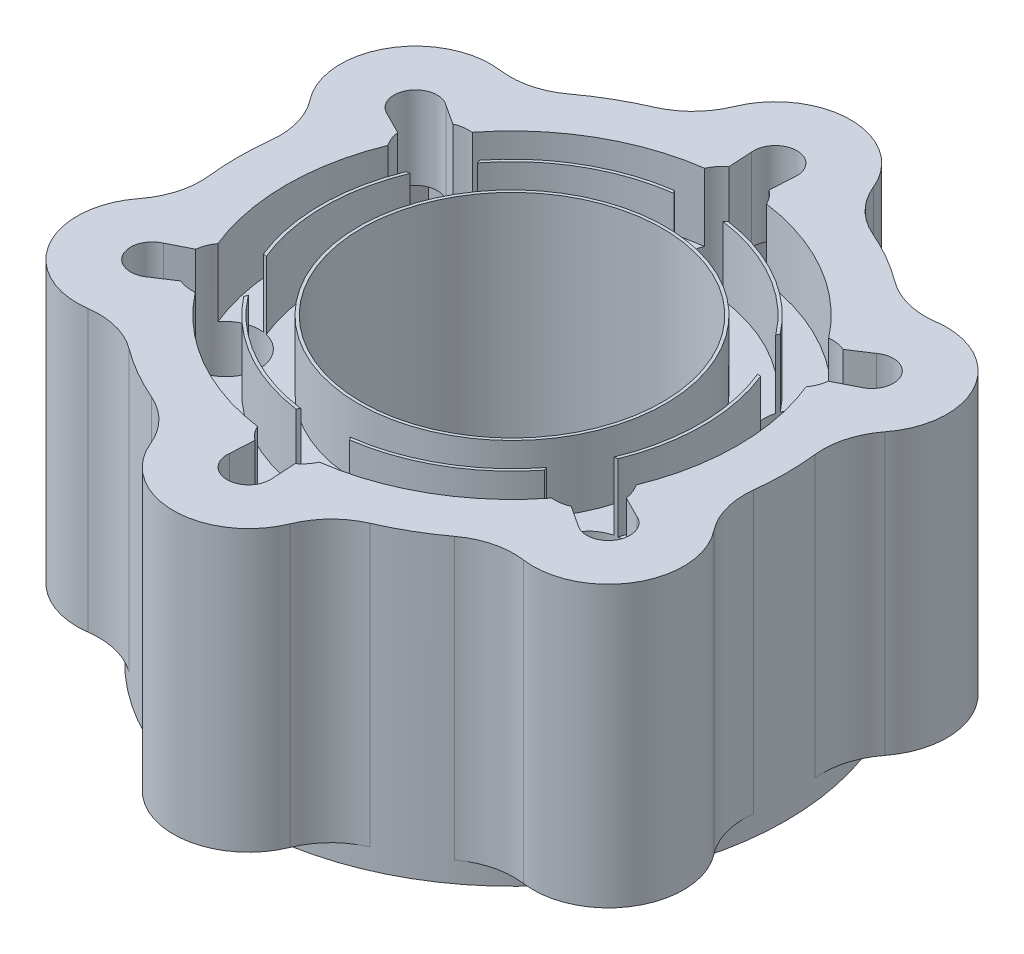
SolidWorks part; units mm, degrees
ref_plane "Front Plane" through (0, 0, 0) normal (0, 0, 1) x (1, 0, 0)
ref_plane "Top Plane" through (0, 0, 0) normal (0, 1, 0) x (1, 0, 0)
ref_plane "Right Plane" through (0, 0, 0) normal (1, 0, 0) x (0, 0, -1)
sketch "Sketch1" plane through (0, 0, 0) normal (0, 1, 0) x (1, 0, 0)
  circle A0 centre (0, 0) radius 27.875
  circle A1 centre (0, 0) radius 37
  circle A2 centre (0, 27.875) radius 2.375
  circle A3 centre (24.1405, 13.9375) radius 2.375
  circle A4 centre (24.1405, -13.9375) radius 2.375
  circle A5 centre (0, -27.875) radius 2.375
  circle A6 centre (-24.1405, -13.9375) radius 2.375
  circle A7 centre (-24.1405, 13.9375) radius 2.375
  circle A8 centre (0, 0) radius 20
  point P18 (0, 0)
  dimension "D1" = 55.75
  dimension "D2" = 74
  dimension "D3" = 4.75
  dimension "D5" = 40
  dimension "D4" = 6
extrude "Boss-Extrude1" add sketch "Sketch1" along normal blind 8 contours A1 A7 A0 A2 A3 A4 A5 A6 | A7 A0 A6 A5 A4 A3 A2 A8 region at (26.4399, 0, 5.8899) region at (-35.9535, 0, 0)
sketch "Sketch2" plane through (0, 8, 0) normal (0, 1, 0) x (1, 0, 0)
  circle A0 centre (0, 27.875) radius 4.5
  circle A1 centre (0, 0) radius 37
  circle A2 centre (0, 0) radius 37
  circle A3 centre (24.1405, 13.9375) radius 4.5
  circle A4 centre (24.1405, -13.9375) radius 4.5
  circle A5 centre (0, -27.875) radius 4.5
  circle A6 centre (-24.1405, -13.9375) radius 4.5
  circle A7 centre (-24.1405, 13.9375) radius 4.5
  circle A8 centre (0, 0) radius 20 construction
  circle A9 centre (0, 0) radius 20
  dimension "D2" = 9
  dimension "D1" = 0
extrude "Boss-Extrude2" add sketch "Sketch2" along normal offset from surface (32 mm away) 40 up to face at (-24.1405, 0, -11.5625)
sketch "Sketch3" plane through (0, 40, 0) normal (0, 1, 0) x (1, 0, 0)
  circle A0 centre (0, 0) radius 45
  circle A1 centre (0, 27.875) radius 4.5 construction
  circle A2 centre (24.1405, 13.9375) radius 4.5 construction
  circle A3 centre (24.1405, -13.9375) radius 4.5 construction
  circle A4 centre (0, -27.875) radius 4.5 construction
  circle A5 centre (0, 0) radius 20 construction
  circle A6 centre (-24.1405, 13.9375) radius 4.5 construction
  circle A7 centre (-24.1405, -13.9375) radius 4.5 construction
  circle A8 centre (0, 0) radius 20
  circle A9 centre (-24.1405, 13.9375) radius 4.5
  circle A10 centre (-24.1405, -13.9375) radius 4.5
  circle A11 centre (0, -27.875) radius 4.5
  circle A12 centre (24.1405, -13.9375) radius 4.5
  circle A13 centre (24.1405, 13.9375) radius 4.5
  circle A14 centre (0, 27.875) radius 4.5
  dimension "D1" = 90
extrude "Boss-Extrude3" add sketch "Sketch3" against normal offset from surface (37.25 mm away) 2.75 up to face at (-24.1405, 0, -11.5625)
sketch "Sketch4" plane through (0, 40, 0) normal (0, 1, 0) x (1, 0, 0)
  line L0 (-10, 35) -> (10, 35) construction
  circle A0 centre (0, 0) radius 35
  circle A1 centre (0, 35) radius 2.875
  circle A2 centre (30.3109, 17.5) radius 2.875
  circle A3 centre (30.3109, -17.5) radius 2.875
  circle A4 centre (0, -35) radius 2.875
  circle A5 centre (-30.3109, -17.5) radius 2.875
  circle A6 centre (-30.3109, 17.5) radius 2.875
  circle A7 centre (0, 35) radius 10
  circle A8 centre (30.3109, 17.5) radius 10
  circle A9 centre (30.3109, -17.5) radius 10
  circle A10 centre (0, -35) radius 10
  circle A11 centre (-30.3109, -17.5) radius 10
  circle A12 centre (-30.3109, 17.5) radius 10
  circle A13 centre (0, 0) radius 45 construction
  circle A14 centre (0, 0) radius 36.4005
  point P17 (0, 0)
  circle M17 centre (0, 0) radius 45
  dimension "D1" = 70
  dimension "D2" = 5.75
  dimension "D3" = 6
extrude "Cut-Extrude2" cut sketch "Sketch4" against normal up to next contours A14 A7 A12 M17 | A14 A8 A7 M17 | A14 A9 A8 M17 | A14 A10 A9 M17 | A14 A11 A10 M17 | A14 A12 A11 M17 | A1 | A2 | A3 | A4 | A5 | A6 region at (40.4878, 40, 0) region at (20.2439, 40, -35.0635) region at (20.2439, 40, 35.0635) region at (-20.2439, 40, -35.0635) region at (-20.2439, 40, 35.0635) region at (-40.4878, 40, 0)
sketch "Sketch5" plane through (0, 0, 0) normal (0, -1, 0) x (1, 0, 0)
  circle A0 centre (0, 0) radius 36.4005
  arc A1 (-10, 35) -> (-25.3109, 26.1603) centre (0, 0) ccw construction
  circle A2 centre (0, 0) radius 37
  arc A3 (-2.1227, 36.9391) -> (-9.9802, 35.6286) centre (0, 0) ccw construction
extrude "Cut-Extrude3" cut sketch "Sketch5" against normal up to surface (2.75 mm away) up to face at (0, 2.75, 38.9667)
sketch "Sketch6" plane through (0, 0, 0) normal (0, -1, 0) x (1, 0, 0)
  line L0 (32.6636, 21.575) -> (27.9582, 21.575)
  line L1 (2.3527, 39.075) -> (-2.3527, 39.075)
  line L2 (-2.3527, 39.075) -> (-4.7054, 35)
  line L3 (-4.7054, 35) -> (-2.3527, 30.925)
  line L4 (-2.3527, 30.925) -> (2.3527, 30.925)
  line L5 (2.3527, 30.925) -> (4.7054, 35)
  line L6 (4.7054, 35) -> (2.3527, 39.075)
  line L7 (27.9582, 21.575) -> (25.6055, 17.5)
  line L8 (25.6055, 17.5) -> (27.9582, 13.425)
  line L9 (27.9582, 13.425) -> (32.6636, 13.425)
  line L10 (32.6636, 13.425) -> (35.0163, 17.5)
  line L11 (35.0163, 17.5) -> (32.6636, 21.575)
  line L12 (35.0163, -17.5) -> (32.6636, -13.425)
  line L13 (32.6636, -13.425) -> (27.9582, -13.425)
  line L14 (27.9582, -13.425) -> (25.6055, -17.5)
  line L15 (25.6055, -17.5) -> (27.9582, -21.575)
  line L16 (27.9582, -21.575) -> (32.6636, -21.575)
  line L17 (32.6636, -21.575) -> (35.0163, -17.5)
  line L18 (2.3527, -39.075) -> (4.7054, -35)
  line L19 (4.7054, -35) -> (2.3527, -30.925)
  line L20 (2.3527, -30.925) -> (-2.3527, -30.925)
  line L21 (-2.3527, -30.925) -> (-4.7054, -35)
  line L22 (-4.7054, -35) -> (-2.3527, -39.075)
  line L23 (-2.3527, -39.075) -> (2.3527, -39.075)
  line L24 (-32.6636, -21.575) -> (-27.9582, -21.575)
  line L25 (-27.9582, -21.575) -> (-25.6055, -17.5)
  line L26 (-25.6055, -17.5) -> (-27.9582, -13.425)
  line L27 (-27.9582, -13.425) -> (-32.6636, -13.425)
  line L28 (-32.6636, -13.425) -> (-35.0163, -17.5)
  line L29 (-35.0163, -17.5) -> (-32.6636, -21.575)
  line L30 (-35.0163, 17.5) -> (-32.6636, 13.425)
  line L31 (-32.6636, 13.425) -> (-27.9582, 13.425)
  line L32 (-27.9582, 13.425) -> (-25.6055, 17.5)
  line L33 (-25.6055, 17.5) -> (-27.9582, 21.575)
  line L34 (-27.9582, 21.575) -> (-32.6636, 21.575)
  line L35 (-32.6636, 21.575) -> (-35.0163, 17.5)
  line L36 (32.6636, 21.575) -> (27.9582, 13.425) construction
  circle A0 centre (0, 35) radius 4.075 construction
  arc A2 (30.1663, 20.3714) -> (32.7253, 15.9391) centre (30.3109, 17.5) ccw construction
  point P1 (30.3109, 17.5)
  point P41 (0, 0)
  dimension "D1" = 8.15
  dimension "D2" = 6
extrude "Cut-Extrude4" cut sketch "Sketch6" against normal offset from surface (29 mm away) 11 up to face at (-26.522, 40, -15.3125)
sketch "Sketch7" plane through (0, 40, 0) normal (0, 1, 0) x (1, 0, 0)
  line L0 (-2.875, 35) -> (2.875, 35) construction
  line L1 (-2.875, 35) -> (-2.6792, 31.4905)
  line L2 (2.875, 35) -> (2.6792, 31.4905)
  line L3 (-2.875, 35) -> (2.875, 35)
  line L4 (-2.6792, 31.4905) -> (2.6792, 31.4905)
  line L5 (28.8734, 19.9898) -> (25.932, 18.0655)
  line L6 (25.932, 18.0655) -> (28.6112, 13.425)
  line L7 (31.7484, 15.0102) -> (28.6112, 13.425)
  line L8 (28.8734, 19.9898) -> (31.7484, 15.0102)
  line L9 (31.7484, -15.0102) -> (28.6112, -13.425)
  line L10 (28.6112, -13.425) -> (25.932, -18.0655)
  line L11 (28.8734, -19.9898) -> (25.932, -18.0655)
  line L12 (31.7484, -15.0102) -> (28.8734, -19.9898)
  line L13 (2.875, -35) -> (2.6792, -31.4905)
  line L14 (2.6792, -31.4905) -> (-2.6792, -31.4905)
  line L15 (-2.875, -35) -> (-2.6792, -31.4905)
  line L16 (2.875, -35) -> (-2.875, -35)
  line L17 (-28.8734, -19.9898) -> (-25.932, -18.0655)
  line L18 (-25.932, -18.0655) -> (-28.6112, -13.425)
  line L19 (-31.7484, -15.0102) -> (-28.6112, -13.425)
  line L20 (-28.8734, -19.9898) -> (-31.7484, -15.0102)
  line L21 (-31.7484, 15.0102) -> (-28.6112, 13.425)
  line L22 (-28.6112, 13.425) -> (-25.932, 18.0655)
  line L23 (-28.8734, 19.9898) -> (-25.932, 18.0655)
  line L24 (-31.7484, 15.0102) -> (-28.8734, 19.9898)
  circle A0 centre (0, 35) radius 2.875 construction
  point P10 (25.932, 18.0655)
  point P31 (0, 0)
  dimension "D1" = 6
extrude "Cut-Extrude6" cut sketch "Sketch7" against normal up to surface (11 mm away) up to face at (0, 29, -35.1842)
fillet "Fillet1" radius 10 12 edges at (-35.3109, 21.375, -8.8397) (-35.3109, 21.375, 8.8397) (-25.3109, 21.375, 26.1603) (-10, 21.375, 35) (10, 21.375, 35) (25.3109, 21.375, 26.1603) (35.3109, 21.375, 8.8397) (35.3109, 21.375, -8.8397) (25.3109, 21.375, -26.1603) (10, 21.375, -35) (-25.3109, 21.375, -26.1603) (-10, 21.375, -35)
sketch "Sketch8" plane through (0, 40, 0) normal (0, 1, 0) x (1, 0, 0)
  circle A0 centre (0, 0) radius 30
  dimension "D1" = 60
extrude "Cut-Extrude7" cut sketch "Sketch8" against normal blind 9
sketch "Sketch9" plane through (0, 31, 0) normal (0, 1, 0) x (1, 0, 0)
  line L0 (0, 20.4) -> (0, 20) construction
  line L1 (-25.4, 0) -> (-25, 0) construction
  circle A0 centre (0, 0) radius 20 construction
  circle A1 centre (0, 0) radius 20
  circle A2 centre (0, 0) radius 20.4
  circle A3 centre (0, 0) radius 25
  circle A4 centre (0, 0) radius 25.4
  arc A5 (-28.6112, 13.425) -> (-25.932, 18.0655) centre (-24.1405, 13.9375) ccw construction
  arc A6 (-23.6836, -18.4143) -> (-27.789, -11.3035) centre (-24.1405, -13.9375) ccw construction
  arc A7 (4.1054, -29.7178) -> (-4.1054, -29.7178) centre (0, -27.875) ccw construction
  arc A8 (28.6112, -13.425) -> (25.932, -18.0655) centre (24.1405, -13.9375) ccw construction
  arc A9 (23.6836, 18.4143) -> (27.789, 11.3035) centre (24.1405, 13.9375) ccw construction
  arc A10 (-2.6792, 31.4905) -> (2.6792, 31.4905) centre (0, 27.875) ccw construction
  arc A11 (-28.6112, 13.425) -> (-25.932, 18.0655) centre (-24.1405, 13.9375) ccw
  arc A12 (-23.6836, -18.4143) -> (-27.789, -11.3035) centre (-24.1405, -13.9375) ccw
  arc A13 (4.1054, -29.7178) -> (-4.1054, -29.7178) centre (0, -27.875) ccw
  arc A14 (28.6112, -13.425) -> (25.932, -18.0655) centre (24.1405, -13.9375) ccw
  arc A15 (23.6836, 18.4143) -> (27.789, 11.3035) centre (24.1405, 13.9375) ccw
  arc A16 (-2.6792, 31.4905) -> (2.6792, 31.4905) centre (0, 27.875) ccw
  circle M7 centre (0, 0) radius 20
  arc M9 (-27.789, -11.3035) -> (-23.6836, -18.4143) centre (-24.1405, -13.9375) cw
  arc M11 (-4.1054, -29.7178) -> (4.1054, -29.7178) centre (0, -27.875) cw
  arc M13 (23.6836, -18.4143) -> (27.789, -11.3035) centre (24.1405, -13.9375) cw
  arc M15 (27.789, 11.3035) -> (23.6836, 18.4143) centre (24.1405, 13.9375) cw
  arc M17 (4.1054, 29.7178) -> (-4.1054, 29.7178) centre (0, 27.875) cw
  arc M19 (-23.6836, 18.4143) -> (-27.789, 11.3035) centre (-24.1405, 13.9375) cw
  dimension "D1" = 0.4
  dimension "D2" = 50
extrude "Boss-Extrude4" add sketch "Sketch9" along normal up to surface (9 mm away) contours A4 A3 M17 M19 | A4 A3 M15 M17 | A4 A3 M13 M15 | A4 A3 M11 M13 | A4 A3 M9 M11 | A4 A3 M19 M9 | A2 M7 region at (-20.3423, 31, 0) region at (24.7093, 31, -4.9107) region at (12.5972, 31, -21.819) region at (19.7196, 31, 15.5165) region at (-12.5972, 31, -21.819) region at (-3.5779, 31, 24.8359) region at (-25.1926, 31, 0) up to face at (0, 40, 0)
